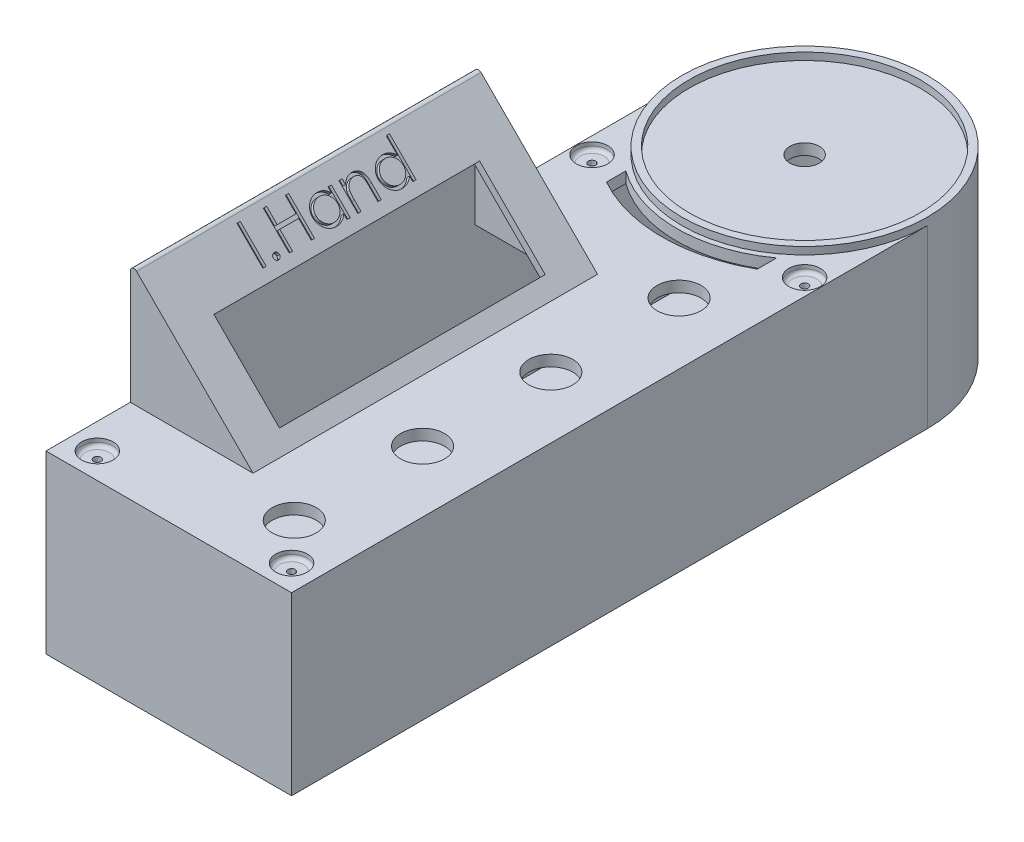
SolidWorks part; units mm, degrees
ref_plane "Front Plane" through (0, 0, 0) normal (0, 0, 1) x (1, 0, 0)
ref_plane "Top Plane" through (0, 0, 0) normal (0, 1, 0) x (1, 0, 0)
ref_plane "Right Plane" through (0, 0, 0) normal (1, 0, 0) x (0, 0, -1)
sketch "Sketch1" plane through (0, 0, 0) normal (0, 0, 1) x (1, 0, 0)
  line L6 (0, 0) -> (0, 47) construction
  line L8 (-31.5, 48) -> (-31.5, 50)
  line L9 (-31.5, 50) -> (-33.5, 50)
  line L10 (-33.5, 50) -> (-33.5, 0)
  line L11 (-33.5, 0) -> (0, 0)
  line L13 (0, 24.8) -> (-8.2, 24.8)
  line L14 (-31.5, 2) -> (-8.2, 2)
  line L17 (-31.5, 45) -> (-31.5, 2)
  line L18 (-8.2, 2) -> (-8.2, 24.8)
  line L19 (0, 0) -> (0, 24.8)
  line L20 (-4, 48) -> (-4, 45)
  line L23 (-31.5, 48) -> (-4, 48)
  line L24 (-31.5, 45) -> (-4, 45)
  dimension "D1" = 33.5
  dimension "D2" = 8
  dimension "D3" = 2
  dimension "D4" = 50
  dimension "D5" = 3
  dimension "D6" = 8.2
  dimension "D7" = 2
  dimension "D8" = 2
  dimension "D9" = 24.8
revolve "Revolve1" add sketch "Sketch1" angle 360 about L6
sketch "Sketch4" plane through (0, 0, 0) normal (0, 0, 1) x (1, 0, 0)
  line L3 (33.5, 0) -> (-33.5, 0)
  line L4 (-31.5, 45) -> (-31.5, 2)
  line L5 (-31.5, 2) -> (31.5, 2)
  line L6 (31.5, 2) -> (31.5, 45)
  line L7 (31.5, 45) -> (-31.5, 45)
  line L8 (31.5, 48) -> (33.5, 48)
  line L9 (-31.5, 48) -> (31.5, 48)
  line L10 (33.5, 48) -> (33.5, 0)
  line L11 (-31.5, 48) -> (-33.5, 48)
  line L12 (-33.5, 48) -> (-33.5, 0)
  dimension "D4" = 2
extrude "Boss-Extrude2" add sketch "Sketch4" along normal blind 173.5
sketch "Sketch6" plane through (0, 48, 0) normal (0, 1, 0) x (1, 0, 0)
  line L0 (4, 0) -> (-4, 0) construction
  circle A0 centre (0, 0) radius 4
extrude "Cut-Extrude1" cut sketch "Sketch6" against normal blind 3
sketch "Sketch9" plane through (0, 0, 173.5) normal (0, 0, 1) x (1, 0, 0)
  line L0 (-31.5, 45) -> (-31.5, 2)
  line L1 (-31.5, 2) -> (31.5, 2)
  line L2 (31.5, 2) -> (31.5, 45)
  line L3 (31.5, 45) -> (-31.5, 45)
extrude "Cut-Extrude2" cut sketch "Sketch9" against normal blind 173.5
sketch "Sketch10" plane through (0, 2, 0) normal (0, 1, 0) x (1, 0, 0)
  line L0 (-8.2, 0) -> (8.2, 0) construction
  circle A0 centre (0, 0) radius 8.2
extrude "Boss-Extrude3" add sketch "Sketch10" along normal blind 22.8
sketch "Sketch11" plane through (0, 0, 173.5) normal (0, 0, 1) x (1, 0, 0)
  line L1 (-31.5, 2) -> (31.5, 2)
  line L2 (-31.5, 2) -> (-31.5, 45)
  line L3 (-31.5, 45) -> (31.5, 45)
  line L4 (31.5, 2) -> (31.5, 45)
extrude "Boss-Extrude4" add sketch "Sketch11" against normal blind 2
sketch "Sketch13" plane through (0, 2, 0) normal (0, 1, 0) x (1, 0, 0)
  line L0 (-26.5, -161.5) -> (-26.5, -171.5)
  line L1 (-31.5, -171.5) -> (-21.5, -171.5)
  line L2 (-31.5, -171.5) -> (-31.5, -161.5)
  line L3 (-31.5, -161.5) -> (-21.5, -161.5)
  line L4 (-21.5, -171.5) -> (-21.5, -161.5)
  line L5 (31.5, -171.5) -> (21.5, -171.5)
  line L6 (31.5, -171.5) -> (31.5, -161.5)
  line L7 (31.5, -161.5) -> (21.5, -161.5)
  line L8 (21.5, -171.5) -> (21.5, -161.5)
  line L9 (-26.5, -171.5) -> (-21.5, -166.5)
  line L10 (-21.5, -166.5) -> (-31.5, -166.5)
  line L11 (26.5, -161.5) -> (26.5, -171.5)
  line L12 (26.5, -171.5) -> (21.5, -166.5)
  line L13 (21.5, -166.5) -> (31.5, -166.5)
  circle A0 centre (-26.5, -166.5) radius 3
  circle A1 centre (26.5, -166.5) radius 3
  dimension "D1" = 10
  dimension "D2" = 10
  dimension "D3" = 10
extrude "Boss-Extrude5" add sketch "Sketch13" along normal blind 43 contours A0 | A1
sketch "Sketch14" plane through (0, 2, 0) normal (0, 1, 0) x (1, 0, 0)
  circle A0 centre (-26.5, -166.5) radius 1
  circle A1 centre (26.5, -166.5) radius 1
extrude "Cut-Extrude3" cut sketch "Sketch14" along normal blind 46
sketch "Sketch15" plane through (0, 48, 0) normal (0, 1, 0) x (1, 0, 0)
  circle A0 centre (-26.5, -166.5) radius 4.3
  circle A1 centre (26.5, -166.5) radius 4.3
extrude "Cut-Extrude4" cut sketch "Sketch15" against normal blind 2
fillet "Fillet1" radius 1 2 edges at (26.5, 46, 170.8) (-26.5, 46, 170.8)
sketch "Sketch16" plane through (0, 48, 0) normal (0, 1, 0) x (1, 0, 0)
  line L0 (0, -173.5) -> (0, -33.5)
  line L1 (33.5, -173.5) -> (-33.5, -173.5) construction
  line L2 (0, -103.5) -> (-33.5, -103.5)
  line L3 (-33.5, -173.5) -> (-33.5, 0) construction
  line L4 (0, -103.5) -> (0, -150.5)
  line L5 (-29.9, -148.5) -> (-3.6, -148.5)
  line L6 (-29.9, -148.5) -> (-29.9, -58.5)
  line L7 (-29.9, -58.5) -> (-3.6, -58.5)
  line L8 (-3.6, -148.5) -> (-3.6, -58.5)
  line L9 (-29.9, -148.5) -> (-3.6, -58.5) construction
  line L10 (-29.9, -58.5) -> (-3.6, -148.5) construction
  line L11 (0, -150.5) -> (-33.5, -150.5)
  line L12 (-33.5, -150.5) -> (-33.5, -56.5)
  line L13 (-33.5, -56.5) -> (0, -56.5)
  line L14 (0, -56.5) -> (0, -103.5)
  arc A0 (-33.5, 0) -> (33.5, 0) centre (0, 0) ccw construction
  point P11 (-16.75, -103.5)
  point P20 (0, 0)
  dimension "D1" = 90
  dimension "D2" = 26.3
  dimension "D3" = 2
  dimension "D4" = 2
sketch "Sketch19" plane through (0, 48, 0) normal (0, 1, 0) x (1, 0, 0)
  line L0 (0, -173.5) -> (0, -33.5) construction
  line L1 (0, -173.5) -> (0, -33.5)
  line L2 (0, -103.5) -> (33.5, -103.5)
  line L3 (33.5, -173.5) -> (33.5, 0) construction
  line L4 (33.5, -103.5) -> (16.75, -103.5)
  line L5 (16.75, -103.5) -> (16.75, -68.5)
  line L7 (16.75, -68.5) -> (16.75, -33.5)
  line L8 (0, -68.5) -> (33.5, -68.5)
  line L9 (0, -138.5) -> (33.5, -138.5)
  line L10 (16.75, -103.5) -> (16.75, -138.5)
  line L11 (16.75, -138.5) -> (16.75, -173.5)
  line L12 (33.5, -173.5) -> (-33.5, -173.5) construction
  circle A0 centre (16.75, -51) radius 6
  circle A1 centre (16.75, -86) radius 6
  circle A2 centre (16.75, -121) radius 6
  circle A3 centre (16.75, -156) radius 6
extrude "Cut-Extrude5" cut sketch "Sketch19" against normal blind 3 contours A0 | A1 | A2 | A3
ref_plane "Plane2" through (0, 0, 56.5) normal (0, 0, 1) x (1, 0, 0)
sketch "Sketch20" plane through (0, 0, 56.5) normal (0, 0, 1) x (1, 0, 0)
  line L0 (0, 48) -> (-33.5, 81.5)
  line L1 (0, 48) -> (-33.5, 48) construction
  line L2 (-33.5, 81.5) -> (-33.5, 48)
  line L3 (-33.5, 48) -> (0, 48)
  line L4 (-33.5, 48) -> (-33.5, 0) construction
  line L5 (-4.8284, 50) -> (-31.5, 76.6716)
  line L6 (-31.5, 76.6716) -> (-31.5, 50)
  line L7 (-31.5, 50) -> (-4.8284, 50)
  point P7 (-33.5, 77.9675)
  point P8 (0, 48)
  dimension "D1" = 45
  dimension "D2" = 2
extrude "Boss-Extrude6" add sketch "Sketch20" along normal up to vertex (94 mm away) up to point (-33.5, 48, 150.5)
sketch "Sketch21" plane through (0, 50, 0) normal (0, 1, 0) x (1, 0, 0)
  line L1 (-31.5, -150.5) -> (-4.8284, -150.5)
  line L2 (-31.5, -150.5) -> (-31.5, -56.5)
  line L3 (-31.5, -56.5) -> (-4.8284, -56.5)
  line L4 (-4.8284, -150.5) -> (-4.8284, -56.5)
extrude "Cut-Extrude6" cut sketch "Sketch21" against normal blind 13
fillet "Fillet2" radius 1 2 edges at (-33.5, 81.5, 103.5) (-31.5, 76.6716, 103.5)
sketch "Sketch22" plane through (0, 0, 150.5) normal (0, 0, 1) x (1, 0, 0)
  line L1 (-33.5, 48) -> (-33.5, 46)
  line L2 (-33.5, 46) -> (0, 46)
  line L3 (0, 46) -> (0, 48)
  line L7 (0, 48) -> (-31.7929, 79.7929)
  line L8 (-33.5, 79.0858) -> (-33.5, 48)
  line L9 (-33.5, 48) -> (-31.5, 48)
  line L10 (-31.5, 48) -> (-31.5, 74.2574)
  line L11 (-29.7929, 74.9645) -> (-4.8284, 50)
  line L12 (-4.8284, 50) -> (-4.8284, 48)
  line L13 (-4.8284, 48) -> (0, 48)
  line L14 (0, 48) -> (-31.7929, 79.7929)
  line L15 (-33.5, 79.0858) -> (-33.5, 48)
  arc A2 (-31.7929, 79.7929) -> (-33.5, 79.0858) centre (-32.5, 79.0858) ccw
  arc A3 (-29.7929, 74.9645) -> (-31.5, 74.2574) centre (-30.5, 74.2574) ccw
  arc A4 (-31.7929, 79.7929) -> (-33.5, 79.0858) centre (-32.5, 79.0858) ccw
  dimension "D2" = 2
  dimension "D1" = 0
extrude "Boss-Extrude8" add sketch "Sketch22" against normal blind 2
sketch "Sketch23" plane through (24, 24, 0) normal (0.7071, 0.7071, 0) x (0, 0, -1)
  line L0 (-56.5, 33.9411) -> (-56.5, 78.9031) construction
  line L1 (-150.5, 33.9411) -> (-56.5, 33.9411)
  line L2 (-150.5, 33.9411) -> (-150.5, 69.2411)
  line L3 (-150.5, 69.2411) -> (-56.5, 69.2411)
  line L4 (-56.5, 33.9411) -> (-56.5, 69.2411)
  line L5 (-103.5, 33.9411) -> (-103.5, 69.2411)
  line L6 (-103.5, 69.2411) -> (-56.5, 51.5911)
  line L7 (-56.5, 51.5911) -> (-150.5, 51.5911)
  line L9 (-139.75, 38.9411) -> (-67.25, 38.9411)
  line L10 (-139.75, 38.9411) -> (-139.75, 64.2411)
  line L11 (-139.75, 64.2411) -> (-67.25, 64.2411)
  line L12 (-67.25, 38.9411) -> (-67.25, 64.2411)
  line L13 (-139.75, 38.9411) -> (-67.25, 64.2411) construction
  line L14 (-139.75, 64.2411) -> (-67.25, 38.9411) construction
  point P12 (-103.5, 51.5911)
  dimension "D1" = 94
  dimension "D2" = 72.5
  dimension "D3" = 5
  dimension "D4" = 25.3
extrude "Cut-Extrude7" cut sketch "Sketch23" against normal blind 2 contours L11 L12 L9 L10
sketch "Sketch24" plane through (0, 0, 56.5) normal (0, 0, -1) x (-1, 0, 0)
  line L0 (4.8284, 45) -> (4.8284, 48) construction
  line L1 (4.8284, 45) -> (31.5, 45) construction
  line L2 (31.5, 45) -> (31.5, 48) construction
  line L3 (4.8284, 48) -> (4.8284, 50) construction
  line L4 (4.8284, 50) -> (29.7929, 74.9645) construction
  line L5 (31.5, 74.2574) -> (31.5, 48) construction
  line L6 (4.8284, 45) -> (4.8284, 48)
  line L7 (4.8284, 45) -> (31.5, 45)
  line L8 (31.5, 45) -> (31.5, 48)
  line L9 (4.8284, 48) -> (4.8284, 50)
  line L10 (4.8284, 50) -> (29.7929, 74.9645)
  line L11 (31.5, 74.2574) -> (31.5, 48)
  arc A0 (31.5, 74.2574) -> (29.7929, 74.9645) centre (30.5, 74.2574) ccw construction
  arc A1 (31.5, 74.2574) -> (29.7929, 74.9645) centre (30.5, 74.2574) ccw
extrude "Boss-Extrude9" add sketch "Sketch24" against normal blind 2
sketch "Sketch25" plane through (0, 48, 0) normal (0, 1, 0) x (1, 0, 0)
  line L0 (0, -173.5) -> (0, -33.5) construction
  line L1 (0, -173.5) -> (0, -33.5)
  line L2 (0, -33.5) -> (33.5, -33.5)
  line L3 (33.5, -173.5) -> (33.5, 0) construction
  line L4 (0, -33.5) -> (-33.5, -33.5)
  line L5 (-33.5, -56.5) -> (-33.5, 0) construction
  line L7 (-33.5, -33.5) -> (-24.5, -33.5)
  line L8 (-33.5, -33.5) -> (-33.5, -24.5)
  line L9 (-33.5, -24.5) -> (-24.5, -24.5)
  line L10 (-24.5, -33.5) -> (-24.5, -24.5)
  line L11 (33.5, -33.5) -> (24.5, -33.5)
  line L12 (33.5, -33.5) -> (33.5, -24.5)
  line L13 (33.5, -24.5) -> (24.5, -24.5)
  line L14 (24.5, -33.5) -> (24.5, -24.5)
  circle A0 centre (29, -29) radius 3
  circle A1 centre (-29, -29) radius 3
  dimension "D1" = 9
  dimension "D2" = 9
  dimension "D3" = 9
extrude "Boss-Extrude10" add sketch "Sketch25" against normal blind 48 contours A1 | A0
sketch "Sketch26" plane through (0, 48, 0) normal (0, 1, 0) x (1, 0, 0)
  circle A0 centre (29, -29) radius 1
  circle A1 centre (-29, -29) radius 1
extrude "Cut-Extrude8" cut sketch "Sketch26" against normal blind 46
sketch "Sketch27" plane through (0, 48, 0) normal (0, 1, 0) x (1, 0, 0)
  circle A0 centre (-29, -29) radius 4.3
  circle A1 centre (29, -29) radius 4.3
extrude "Cut-Extrude9" cut sketch "Sketch27" against normal blind 2
fillet "Fillet3" radius 1 2 edges at (29, 46, 33.3) (-29, 46, 33.3)
sketch "Sketch29" plane through (-33.5, 0, 0) normal (-1, 0, 0) x (0, 0, 1)
  line L0 (103.5, 79.0858) -> (103.5, 0)
  line L1 (150.5, 79.0858) -> (56.5, 79.0858) construction
  line L2 (173.5, 0) -> (0, 0) construction
  line L3 (73.5, 22) -> (73.5, 0)
  line L4 (73.5, 22) -> (133.5, 22)
  line L5 (73.5, 0) -> (133.5, 0)
  line L6 (133.5, 22) -> (133.5, 0)
  line L7 (73.5, 22) -> (133.5, 0) construction
  line L8 (73.5, 0) -> (133.5, 22) construction
  line L9 (75.5, 20) -> (75.5, 2)
  line L10 (75.5, 20) -> (131.5, 20)
  line L11 (75.5, 2) -> (131.5, 2)
  line L12 (131.5, 20) -> (131.5, 2)
  line L13 (75.5, 20) -> (131.5, 2) construction
  line L14 (75.5, 2) -> (131.5, 20) construction
  point P7 (103.5, 11)
  point P8 (103.5, 11)
  dimension "D1" = 22
  dimension "D2" = 60
  dimension "D3" = 0
  dimension "D4" = 2
  dimension "D5" = 2
  dimension "D6" = 2
  dimension "D7" = 2
  dimension "D8" = 0
sketch "Sketch30" plane through (-33.5, 0, 0) normal (-1, 0, 0) x (0, 0, 1)
  line L0 (75.5, 20) -> (75.5, 2) construction
  line L1 (75.5, 20) -> (131.5, 20) construction
  line L2 (75.5, 2) -> (131.5, 2) construction
  line L3 (131.5, 20) -> (131.5, 2) construction
  line L4 (131.5, 20) -> (131.5, 2)
  line L5 (75.5, 2) -> (131.5, 2)
  line L6 (75.5, 20) -> (75.5, 2)
  line L7 (75.5, 20) -> (131.5, 20)
extrude "Cut-Extrude10" cut sketch "Sketch30" against normal blind 2
sketch "Sketch31" plane through (-33.5, 0, 0) normal (-1, 0, 0) x (0, 0, 1)
  line L0 (131.5, 20) -> (131.5, 2) construction
  line L1 (133.5, 22) -> (133.5, 0) construction
  line L2 (75.5, 2) -> (131.5, 2) construction
  line L3 (73.5, 0) -> (133.5, 0) construction
  line L4 (75.5, 20) -> (75.5, 2) construction
  line L5 (75.5, 20) -> (131.5, 20) construction
  line L6 (73.5, 22) -> (73.5, 0) construction
  line L7 (73.5, 22) -> (133.5, 22) construction
  line L8 (131.5, 20) -> (131.5, 2)
  line L9 (133.5, 22) -> (133.5, 0)
  line L10 (75.5, 2) -> (131.5, 2)
  line L11 (73.5, 0) -> (133.5, 0)
  line L12 (75.5, 20) -> (75.5, 2)
  line L13 (75.5, 20) -> (131.5, 20)
  line L14 (73.5, 22) -> (73.5, 0)
  line L15 (73.5, 22) -> (133.5, 22)
extrude "Boss-Extrude11" add sketch "Sketch31" along normal blind 12
fillet "Fillet4" radius 1 3 edges at (-33.5, 11, 133.5) (-33.5, 22, 103.5) (-33.5, 11, 73.5)
sketch "Sketch33" plane through (-45.5, 0, 0) normal (-1, 0, 0) x (0, 0, 1)
  line L0 (131.5, 2) -> (131.5, 20) construction
  line L1 (75.5, 2) -> (131.5, 2) construction
  line L2 (75.5, 20) -> (75.5, 2) construction
  line L3 (131.5, 20) -> (75.5, 20) construction
  line L4 (131.5, 2) -> (131.5, 20)
  line L5 (75.5, 2) -> (131.5, 2)
  line L6 (75.5, 20) -> (75.5, 2)
  line L7 (131.5, 20) -> (75.5, 20)
extrude "Boss-Extrude12" add sketch "Sketch33" against normal blind 2
sketch "Sketch34" plane through (24, 24, 0) normal (0.7071, 0.7071, 0) x (0, 0, -1)
  line L0 (-139.75, 67.2411) -> (-67.25, 67.2411) construction
  line L1 (-139.75, 64.2411) -> (-67.25, 64.2411) construction
  text T0 "I.Hand" font "Century Gothic" height 10
  point P4 (0, 0)
  dimension "D1" = 3
  dimension "D2" = 0
  dimension "D3" = 0
extrude "Cut-Extrude11" cut sketch "Sketch34" against normal blind 1
sketch "Sketch35" plane through (-45.5, 0, 0) normal (-1, 0, 0) x (0, 0, 1)
  line L0 (103.5, 7) -> (76.8, 7)
  line L1 (75.5, 2) -> (131.5, 2)
  line L2 (75.5, 2) -> (75.5, 20)
  line L3 (75.5, 20) -> (131.5, 20)
  line L4 (131.5, 2) -> (131.5, 20)
  line L5 (75.5, 2) -> (131.5, 20) construction
  line L6 (75.5, 20) -> (131.5, 2) construction
  line L7 (133.5, 22) -> (73.5, 22) construction
  line L8 (73.5, 0) -> (133.5, 0) construction
  line L9 (73.5, 22) -> (73.5, 0) construction
  line L10 (133.5, 0) -> (133.5, 22) construction
  line L11 (76.8, 7) -> (86.6, 7)
  line L12 (103.5, 7) -> (130.2, 7)
  line L13 (86.6, 7) -> (86.6, 19)
  line L14 (86.6, 19) -> (99.7, 19)
  line L15 (99.7, 19) -> (99.7, 7)
  line L16 (119.1, 7) -> (119.1, 18.8)
  line L17 (119.1, 18.8) -> (129, 18.8)
  line L18 (129, 18.8) -> (129, 7)
  point P0 (103.5, 11)
  dimension "D1" = 2
  dimension "D2" = 2
  dimension "D3" = 2
  dimension "D4" = 2
  dimension "D5" = 12
  dimension "D6" = 13.1
  dimension "D7" = 19.4
  dimension "D8" = 9.9
  dimension "D9" = 11.8
extrude "Cut-Extrude12" cut sketch "Sketch35" against normal blind 2 contours L15 L14 L13 L0 | L18 L17 L16 L12 region at (-45.5, 13, 93.15) region at (-45.5, 12.9, 124.05)
fillet "Fillet5" radius 1 3 edges at (-45.5, 11, 133.5) (-45.5, 11, 73.5) (-45.5, 22, 103.5)
sketch "Sketch36" plane through (0, 48, 0) normal (0, 1, 0) x (1, 0, 0)
  line L0 (0, -33.5) -> (0, -34.8932)
  line L1 (0, -34.8932) -> (0, -38.8932)
  line L2 (20.5725, -33.5) -> (20.5725, -28.2088)
  line L3 (-20.5725, -28.2088) -> (-20.5725, -33.5)
  arc A0 (-33.5, 0) -> (33.5, 0) centre (0, 0) ccw construction
  arc A1 (0, -34.8932) -> (-20.5725, -28.2088) centre (0, 0.1068) cw
  arc A2 (0, -34.8932) -> (20.5725, -28.2088) centre (0, 0.1068) ccw
  arc A3 (0, -38.8932) -> (-20.5725, -33.5) centre (0, 3.0408) cw
  arc A4 (0, -38.8932) -> (20.5725, -33.5) centre (0, 3.0408) ccw
  point P15 (0, 0)
  point P16 (0, 0)
  dimension "D1" = 5.2912
extrude "Cut-Extrude13" cut sketch "Sketch36" against normal blind 3 and the other way through all contours L1 A4 L2 A2 | A3 L1 A1 L3 region at (10.7626, 48, 34.8016) region at (-10.7626, 48, 34.8016)
fillet "Fillet6" radius 1 3 edges at (-31.5, 11, 75.5) (-31.5, 20, 103.5) (-31.5, 11, 131.5)
sketch "Sketch37" plane through (31.5, 0, 0) normal (-1, 0, 0) x (0, 0, 1)
  line L0 (30.6583, 33.5) -> (171.5, 33.5)
  line L1 (30.6583, 2) -> (30.6583, 45) construction
  line L2 (171.5, 2) -> (171.5, 45) construction
  line L3 (171.5, 45) -> (30.6583, 45) construction
  line L5 (30.6583, 33.5) -> (171.5, 33.5)
  line L6 (30.6583, 33.5) -> (30.6583, 31.4)
  line L7 (30.6583, 31.4) -> (171.5, 31.4)
  line L8 (171.5, 33.5) -> (171.5, 31.4)
  line L9 (30.6583, 35.5) -> (171.5, 35.5)
  line L10 (30.6583, 35.5) -> (30.6583, 29.4)
  line L11 (30.6583, 29.4) -> (171.5, 29.4)
  line L12 (171.5, 35.5) -> (171.5, 29.4)
  line M3 (30.6583, 45) -> (30.6583, 2)
  line M5 (171.5, 2) -> (171.5, 45)
  dimension "D1" = 11.5
  dimension "D2" = 2.1
  dimension "D3" = 2
  dimension "D4" = 2
extrude "Boss-Extrude13" add sketch "Sketch37" along normal blind 4 contours L9 L0 M3 M5 | L11 L7 M3 M5 region at (31.5, 34.5, 101.0792) region at (31.5, 30.4, 101.0792)
fillet "Fillet8" radius 2 1 edges at (31.5, 29.4, 101.0792)
ref_plane "Plane4" through (0, 45, 0) normal (0, -1, 0) x (-1, 0, 0)
